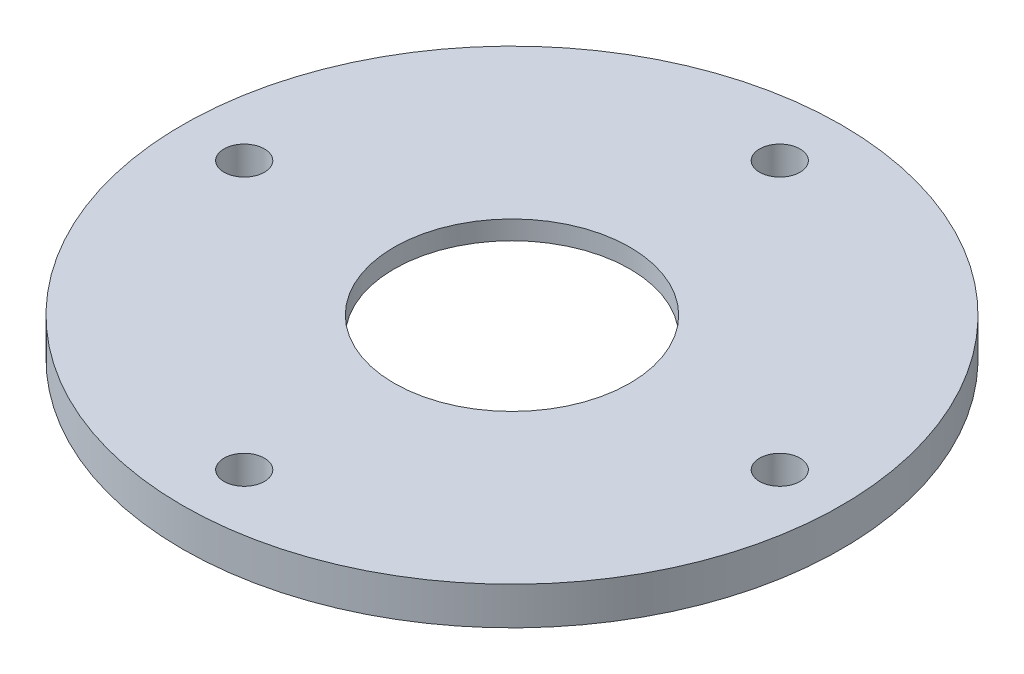
SolidWorks part; units mm, degrees
ref_plane "Front Plane" through (0, 0, 0) normal (0, 0, 1) x (1, 0, 0)
ref_plane "Top Plane" through (0, 0, 0) normal (0, 1, 0) x (1, 0, 0)
ref_plane "Right Plane" through (0, 0, 0) normal (1, 0, 0) x (0, 0, -1)
sketch "Sketch1" plane through (0, 0, 0) normal (0, 0, 1) x (1, 0, 0)
  line L0 (12.3063, 0) -> (12.3063, 1.5875)
  line L1 (12.3063, 1.5875) -> (9.906, 1.5875)
  line L2 (9.906, 1.5875) -> (9.906, 3.175)
  line L3 (9.906, 3.175) -> (27.69, 3.175)
  line L4 (27.69, 3.175) -> (27.69, 0)
  line L5 (27.69, 0) -> (12.3063, 0)
  line L6 (0, 0) -> (0, 23.5305) construction
  dimension "D1" = 12.3063
  dimension "D2" = 27.69
  dimension "D3" = 3.175
  dimension "D4" = 1.5875
  dimension "D5" = 9.906
revolve "Revolve1" add sketch "Sketch1" angle 360 about L6
sketch "Sketch2" plane through (0, 3.175, 0) normal (0, 1, 0) x (1, 0, 0)
  circle A0 centre (0, 0) radius 22.5 construction
  point P3 (0, 22.5)
  point P4 (-22.5, 0)
  point P5 (0, -22.5)
  point P6 (22.5, 0)
  point P7 (7.5914, 44.355)
  dimension "D1" = 45
hole_wizard "M3 Clearance Hole1" positions "Sketch2" profile "Sketch3" hole size "M3" standard "ANSI Metric" end condition up to next
sketch "Sketch3" plane through (22.5, 3.175, 0) normal (1, 0, 0) x (0, 0, 1)
  line L0 (0, 0) -> (0, 3.175)
  line L1 (0, 3.175) -> (1.7, 3.175)
  line L2 (1.7, 3.175) -> (1.7, 0)
  line L5 (1.7, 0) -> (0, 0)
  line L11 (0, -6.35) -> (0, 107.95) construction
  dimension "Thru Hole Dia." = 3.4
  dimension "Thru Hole Depth" = 3.175
